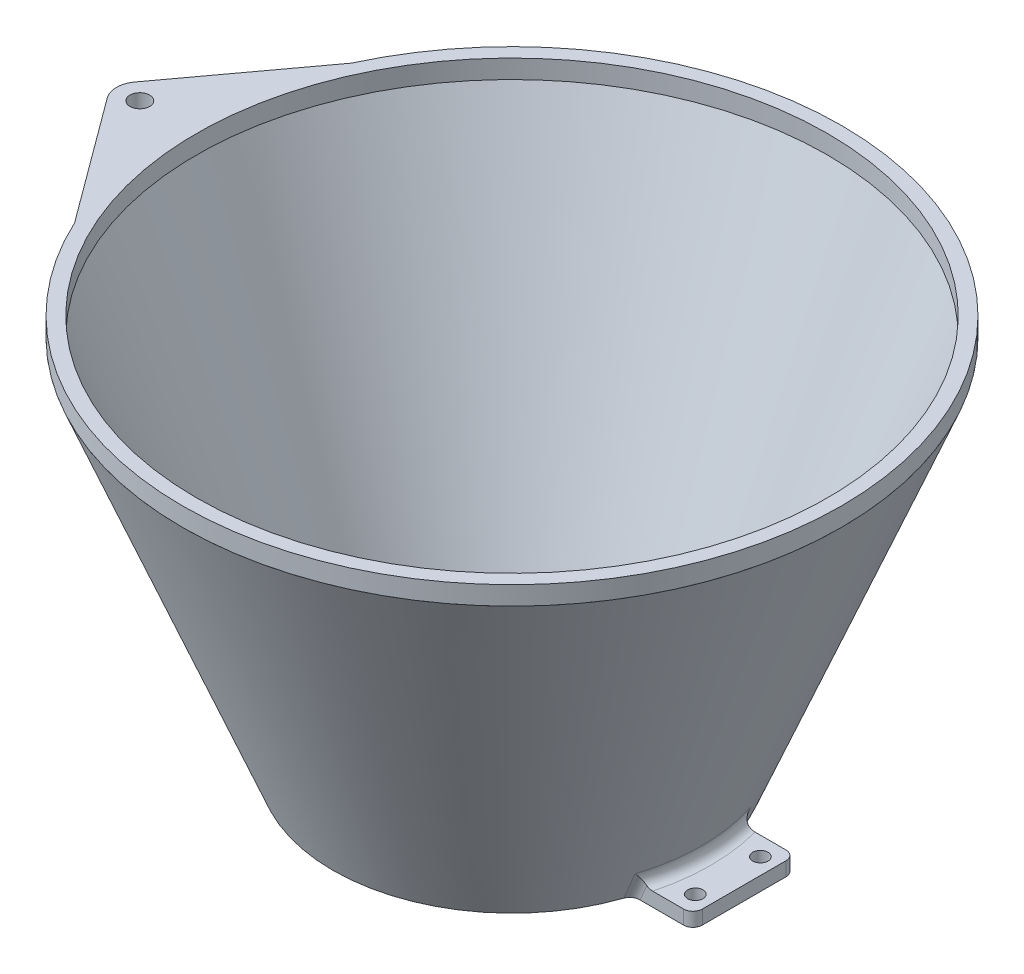
SolidWorks part; units mm, degrees
ref_plane "Front Plane" through (0, 0, 0) normal (0, 0, 1) x (1, 0, 0)
ref_plane "Top Plane" through (0, 0, 0) normal (0, 1, 0) x (1, 0, 0)
ref_plane "Right Plane" through (0, 0, 0) normal (1, 0, 0) x (0, 0, -1)
sketch "Sketch2" plane through (0, 0, 0) normal (0, 0, 1) x (1, 0, 0)
  line L0 (0, 0) -> (35.5, 0) construction
  line L1 (35.5, 0) -> (67.8221, 80)
  line L2 (35.5, 0) -> (38.5, 0) construction
  line L3 (38.5, 0) -> (70.8221, 80)
  line L4 (67.8221, 80) -> (70.8221, 80)
  line L5 (0, 0) -> (0, 42.1787) construction
  line L6 (35.5, 0) -> (38.5, 0)
  point P6 (72.861, 80)
  dimension "D1" = 35.5
  dimension "D2" = 38.5
  dimension "D3" = 80
  dimension "D4" = 112
  dimension "D5" = 80
  dimension "D6" = 0
revolve "Revolve1" add sketch "Sketch2" angle 360 about L5
sketch "Sketch3" plane through (0, 0, 0) normal (0, -1, 0) x (1, 0, 0)
  line L0 (-49.8951, 11) -> (-36.8951, 11)
  line L1 (-49.8951, 11) -> (-49.8951, -11)
  line L2 (-49.8951, -11) -> (-36.8951, -11)
  line L3 (-49.8951, 0) -> (0, 0) construction
  line L4 (0, 0) -> (0, 25.3337) construction
  line L5 (49.8951, -11) -> (36.8951, -11)
  line L6 (49.8951, 11) -> (49.8951, -11)
  line L7 (49.8951, 11) -> (36.8951, 11)
  circle A0 centre (0, 0) radius 38.5 construction
  circle A1 centre (0, 0) radius 38.5 construction
  circle A2 centre (-46.3951, -7) radius 1.65
  arc A3 (-36.8951, -11) -> (-36.8951, 11) centre (0, 0) cw
  circle A4 centre (-46.3951, 7) radius 1.65
  circle A5 centre (46.3951, 7) radius 1.65
  arc A6 (36.8951, -11) -> (36.8951, 11) centre (0, 0) ccw
  circle A7 centre (46.3951, -7) radius 1.65
  dimension "D2" = 3.3
  dimension "D1" = 22
  dimension "D3" = 7
  dimension "D4" = 3.5
  dimension "D5" = 13
extrude "Boss-Extrude1" add sketch "Sketch3" against normal blind 3
fillet "Fillet1" radius 2 10 edges at (49.8951, 1.5, -11) (49.8951, 1.5, 11) (-49.8951, 1.5, 11) (-49.8951, 1.5, -11) (39.7121, 3, 0) (-39.7121, 3, 0)
sketch "Sketch4" plane through (0, 80, 0) normal (0, 1, 0) x (1, 0, 0)
  line L0 (-80, 34.5374) -> (-80, -37.4895) construction
  line L1 (-108.9765, 0) -> (0, 0) construction
  line L7 (-84.0235, 2.9684) -> (-47.3766, 52.6424)
  line L8 (-84.0235, -2.9684) -> (-47.3766, -52.6424)
  line L11 (-95, 27) -> (-65, 27) construction
  line L12 (-65, -27) -> (-65, 27) construction
  line L13 (-95, -27) -> (-65, 27) construction
  line L14 (-95, 27) -> (-65, -27) construction
  circle A4 centre (0, 0) radius 70.8221 construction
  circle A6 centre (-80, 0) radius 2.125
  circle A8 centre (0, 0) radius 67.8221 construction
  circle A9 centre (0, 0) radius 67.8221
  arc A10 (-47.3766, -52.6424) -> (-47.3766, 52.6424) centre (0, 0) ccw
  arc A11 (-84.0235, 2.9684) -> (-84.0235, -2.9684) centre (-80, 0) ccw
  point P13 (-80, 0)
  point P16 (-80, 0)
  circle M13 centre (0, 0) radius 67.8221
  circle M14 centre (0, 0) radius 70.8221
  dimension "D10" = 4.25
  dimension "D2" = 10
  dimension "D4" = 80
  dimension "D7" = 54
  dimension "D8" = 30
extrude "Boss-Extrude2" add sketch "Sketch4" along normal blind 4 separate body contours M14 M13 | M14 | L7 M14 | L8 M14 region at (-74.4612, 80, 0) region at (-56.2936, 80, -41.5305) region at (-55.6667, 80, -41.068) region at (-56.2936, 80, 41.5305)
